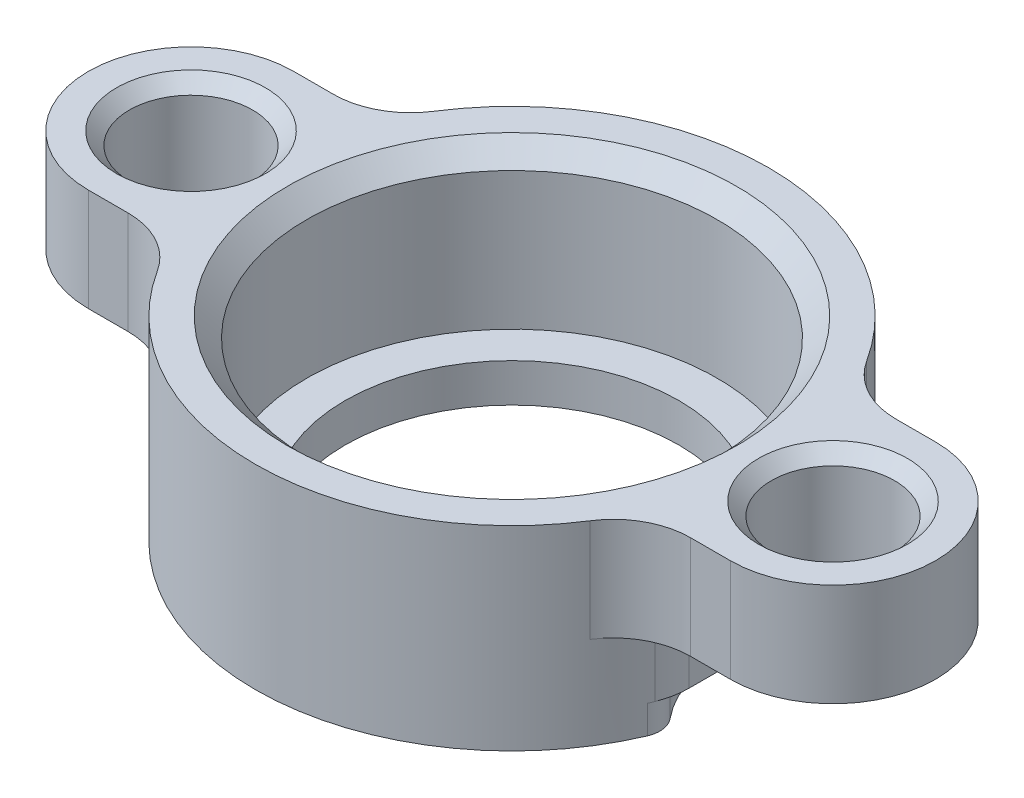
SolidWorks part; units mm, degrees
ref_plane "Plan de face" through (0, 0, 0) normal (0, 0, 1) x (1, 0, 0)
ref_plane "Plan de dessus" through (0, 0, 0) normal (0, 1, 0) x (1, 0, 0)
ref_plane "Plan de droite" through (0, 0, 0) normal (1, 0, 0) x (0, 0, -1)
sketch "Esquisse1" plane through (0, 0, 0) normal (0, 0, 1) x (1, 0, 0)
  line L0 (0, 6.6086) -> (0, -5.0424) construction
  line L1 (-6.5, -4) -> (-6.5, -5.5)
  line L2 (-6.5, -5.5) -> (-10, -5.5)
  line L3 (-10, -5.5) -> (-10, 2.1)
  line L4 (-10, 2.1) -> (-8, 2.1)
  line L9 (-8, 2.1) -> (-8, -4)
  line L10 (-8, -4) -> (-6.5, -4)
  dimension "D1" = 2
  dimension "D2" = 6.1
  dimension "D3" = 8
  dimension "D4" = 4
  dimension "D5" = 1.5
  dimension "D6" = 1.5
revolve "Révolution1" add sketch "Esquisse1" angle 360 about L0
sketch "Esquisse2" plane through (0, 2.1, 0) normal (0, 1, 0) x (1, 0, 0)
  line L0 (-12.5, -4) -> (-9.1652, -4)
  line L1 (-12.5, 4) -> (-9.1652, 4)
  line L2 (0, -4.18) -> (0, 4.18) construction
  line L5 (-9.5, -3.1225) -> (-9.5, 3.1225)
  circle A0 centre (-12.5, 0) radius 2.55 construction
  arc A1 (-12.5, 4) -> (-12.5, -4) centre (-12.5, 0) ccw
  circle A2 centre (0, 0) radius 10 construction
  arc A3 (-9.1652, 4) -> (-9.1652, -4) centre (0, 0) ccw
  circle A7 centre (-12.5, 0) radius 1.7 construction
  circle A9 centre (0, 0) radius 8 construction
  circle M6 centre (0, 0) radius 10
  dimension "D1" = 5.1
  dimension "D2" = 4
  dimension "D4" = 3.4
  dimension "D5" = 1.5
  dimension "D3" = 12.5
extrude "Boss.-Extru.1" add sketch "Esquisse2" against normal blind 4 contours L1 A1 L0 A0 M6 region at (-12.7463, 2.1, 0)
extrude "Enlèv. mat.-Extru.3" cut sketch "Esquisse2<6>" along normal up to surface (-4 mm away) from surface contours L5 M6 region at (-9.7004, 2.1, 0) up to face at (-12.0413, -1.9, 0) starting at face at (0, -5.5, 6.5)
sketch "Esquisse2<6>" plane through (0, 2.1, 0) normal (0, 1, 0) x (1, 0, 0) same geometry as "Esquisse2"
fillet "Congé2" radius 3 2 edges at (-9.5, -3.7, 3.1225) (-9.5, -3.7, -3.1225)
fillet "Congé3" radius 3 2 edges at (-9.1652, 0.1, -4) (-9.1652, 0.1, 4)
mirror "Symétrie1" about plane through (0, 0, 0) normal (1, 0, 0) of "Congé3", "Congé2", "Enlèv. mat.-Extru.3", "Boss.-Extru.1"
hole_wizard "Ø4.8 (4.8) Diameter Hole2" positions "Esquisse8" profile "Esquisse7" hole size "Ø4.8" standard "ANSI Metric"
sketch "Esquisse8" plane through (0, 2.1, 0) normal (0, 1, 0) x (1, 0, 0)
  point P0 (-12.5, 0)
  point P3 (12.5, 0)
sketch "Esquisse7" plane through (-12.5, 2.1, 0) normal (1, 0, 0) x (0, 0, 1)
  line L0 (0, 0) -> (0, 7.8421)
  line L1 (0, 7.8421) -> (2.4, 6.4)
  line L2 (2.4, 6.4) -> (2.4, 0)
  line L5 (2.4, 0) -> (0, 0)
  line L10 (0, 7.8421) -> (-2.4, 6.4) construction
  line L11 (0, -6.35) -> (0, 107.95) construction
  dimension "Hole Dia." = 4.8
  dimension "Hole Depth" = 6.4
  dimension "Drill Angle" = 118
chamfer "Chanfrein1" distance 0.5 angle 45 2 edges at (12.5, 2.1, 2.4) (-12.5, 2.1, 2.4)
sketch "Esquisse9" plane through (0, -5.5, 0) normal (0, -1, 0) x (1, 0, 0)
  circle A0 centre (-12.5, 0) radius 4.5
  circle A1 centre (12.5, 0) radius 4.5
  dimension "D1" = 9
extrude "Enlèv. mat.-Extru.4" cut sketch "Esquisse9" against normal blind 1.1
fillet "Congé4" radius 1 4 edges at (9.4211, -4.95, 3.2818) (9.4211, -4.95, -3.2818) (-9.4211, -4.95, 3.2818) (-9.4211, -4.95, -3.2818)
chamfer "Chanfrein2" distance 0.75 angle 45 1 edges at (0, 2.1, 8)
